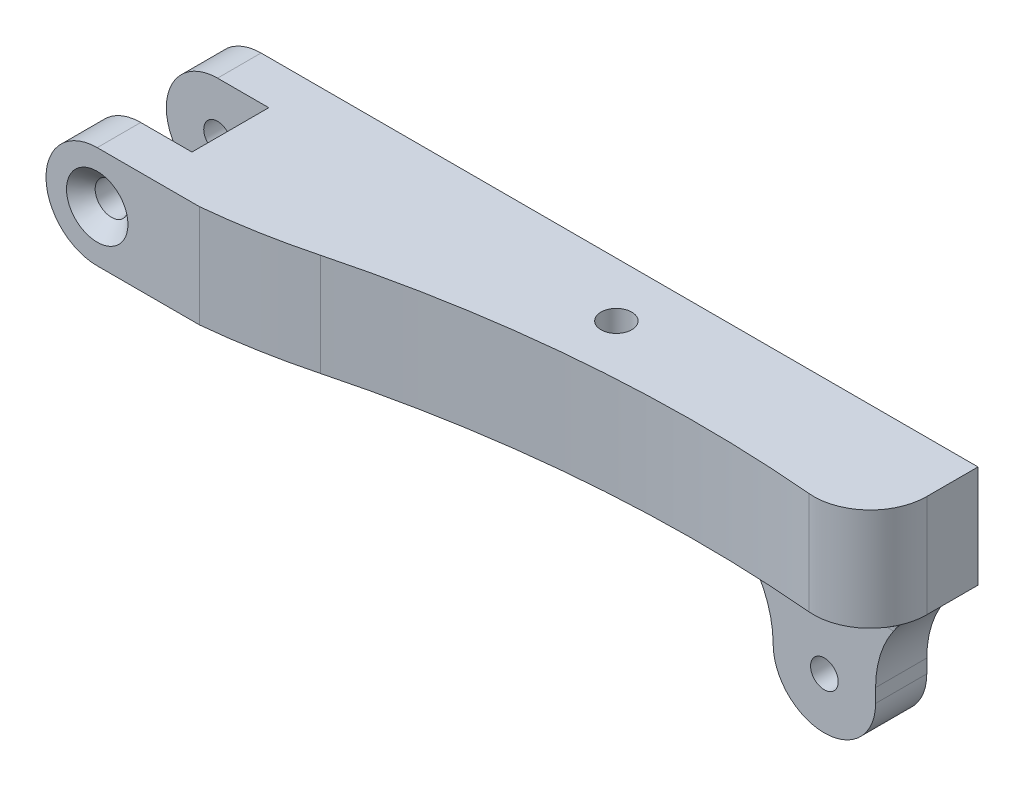
SolidWorks part; units mm, degrees
ref_plane "Plan de face" through (0, 0, 0) normal (0, 0, 1) x (1, 0, 0)
ref_plane "Plan de dessus" through (0, 0, 0) normal (0, 1, 0) x (1, 0, 0)
ref_plane "Plan de droite" through (0, 0, 0) normal (1, 0, 0) x (0, 0, -1)
sketch "Esquisse1" plane through (0, 0, 0) normal (0, 0, 1) x (1, 0, 0)
  line L1 (0, 0) -> (70, 0)
  line L2 (0, 0) -> (0, 10) construction
  line L3 (0, 10) -> (70, 10)
  line L4 (70, 0) -> (70, 10)
  arc A0 (0, 10) -> (0, 0) centre (0, 5) ccw
  circle A1 centre (0, 5) radius 1.6
  dimension "D3" = 3.2
  dimension "D1" = 10
  dimension "D2" = 70
extrude "Boss.-Extru.1" add sketch "Esquisse1" along normal blind 16
sketch "Esquisse2" plane through (0, 10, 0) normal (0, 1, 0) x (1, 0, 0)
  line L5 (5, -4.25) -> (-5, -4.25)
  line L6 (5, -4.25) -> (5, -11.75)
  line L7 (5, -11.75) -> (-5, -11.75)
  line L8 (-5, -4.25) -> (-5, -11.75)
  line L10 (-5, 0) -> (-5, -16) construction
  line L11 (-5, -8) -> (0, -8) construction
  line L12 (0, -16) -> (0, 0) construction
  dimension "D1" = 7.5
  dimension "D2" = 10
extrude "Enlèv. mat.-Extru.1" cut sketch "Esquisse2" against normal through all
sketch "Esquisse3" plane through (0, 0, 0) normal (0, 0, -1) x (-1, 0, 0)
  line L0 (0, 0) -> (-70, 0) construction
  line L1 (-55, 0) -> (-65, 0)
  line L2 (-55, 0) -> (-55, -10) construction
  line L3 (-55, -10) -> (-65, -10) construction
  line L4 (-65, 0) -> (-65, -10) construction
  line L5 (-55, 0) -> (-55, -10)
  line L7 (-65, -10) -> (-65, 0)
  arc A1 (-65, -10) -> (-55, -10) centre (-60, -10) ccw
  point P7 (-60, 0)
  dimension "D4" = 10
  dimension "D2" = 10
  dimension "D3" = 60
extrude "Boss.-Extru.2" add sketch "Esquisse3" against normal blind 5
sketch "Esquisse7" plane through (0, 10, 0) normal (0, 1, 0) x (1, 0, 0)
  line L0 (70, -16) -> (0, -16) construction
  line L1 (70, -10) -> (5, -10) construction
  line L2 (70, -16) -> (70, 0) construction
  line L3 (70, -10) -> (10, -16) construction
  line L4 (5, -11.75) -> (5, -4.25) construction
  line L5 (70, -5) -> (70, -16)
  line L6 (70, -16) -> (10, -16)
  line L7 (65, -5) -> (70, -5) construction
  arc A0 (70, -5) -> (63.9869, -10.5033) centre (64.4751, -5) cw
  arc A1 (10, -16) -> (20, -14.2015) centre (3.5357, 48.6435) ccw
  arc A2 (63.9869, -10.5033) -> (20, -14.2015) centre (52.6158, -138.6973) ccw
  dimension "D1" = 10
  dimension "D2" = 10
  dimension "D3" = 10
extrude "Enlèv. mat.-Extru.2" cut sketch "Esquisse7" against normal blind 10
sketch "Esquisse8" plane through (0, 0, 5) normal (0, 0, 1) x (1, 0, 0)
  circle A0 centre (60, -10) radius 1.35
  arc A1 (55, -10) -> (65, -10) centre (60, -10) ccw construction
  dimension "D1" = 2.7
extrude "Enlèv. mat.-Extru.3" cut sketch "Esquisse8" against normal through all
fillet "Congé1" radius 3 1 edges at (60, 0, 5)
fillet "Congé2" radius 10 2 edges at (55, 0, 4) (65, 0, 4)
sketch "Esquisse9" plane through (0, 0, 0) normal (0, 0, 1) x (1, 0, 0)
  circle A0 centre (0, 5) radius 2.6
  circle A1 centre (0, 5) radius 1.35
  circle A2 centre (0, 5) radius 1.6 construction
  dimension "D1" = 1
  dimension "D2" = 2.7
extrude "Boss.-Extru.3" add sketch "Esquisse9" along normal up to surface (4.25 mm away) up to face at (-1.6, 5, 4.25)
sketch "Esquisse10" plane through (0, 0, 0) normal (0, -1, 0) x (1, 0, 0)
  line L0 (5, 8) -> (45, 8) construction
  line L1 (5, 11.75) -> (5, 4.25) construction
  line L2 (45, 0) -> (45, 8) construction
  line L3 (40, 10.6198) -> (40, 0) construction
  line L4 (0, 0) -> (45, 0) construction
  circle A0 centre (40, 5.3099) radius 1.5
  arc A1 (20, 14.2015) -> (63.9869, 10.5033) centre (52.6158, 138.6973) ccw construction
  dimension "D1" = 3
  dimension "D2" = 5
extrude "Enlèv. mat.-Extru.4" cut sketch "Esquisse10" against normal through all
ref_axis "Axe1" through (0, 5, 20.9681) along (0, 0, -1)
ref_plane "Plan1" through (0, 0, 0) normal (1, 0, 0) x (0, 0, -1)
sketch "Esquisse11" plane through (0, 0, 0) normal (1, 0, 0) x (0, 0, -1)
  line L0 (-13, 5) -> (-16, 8)
  line L1 (-16, 8) -> (-16, 2) construction
  line L2 (-16, 2) -> (-13, 5) construction
  line L3 (-20.9681, 5) -> (-17.2181, 5) construction
  line L4 (-16, 0) -> (-16, 10) construction
  line L5 (-16, 5) -> (-13, 5)
  line L6 (-16, 8) -> (-16, 5)
  line L7 (-16, 5) -> (0, 5) construction
  point P3 (-16, 5)
  dimension "D1" = 6
  dimension "D2" = 16
revolve "Enlèvement de matière-Révolution2" cut sketch "Esquisse11" angle 360 about L5
chamfer "Chamfer1" distance 5 angle 45 1 edges at (5, 0, 8)
